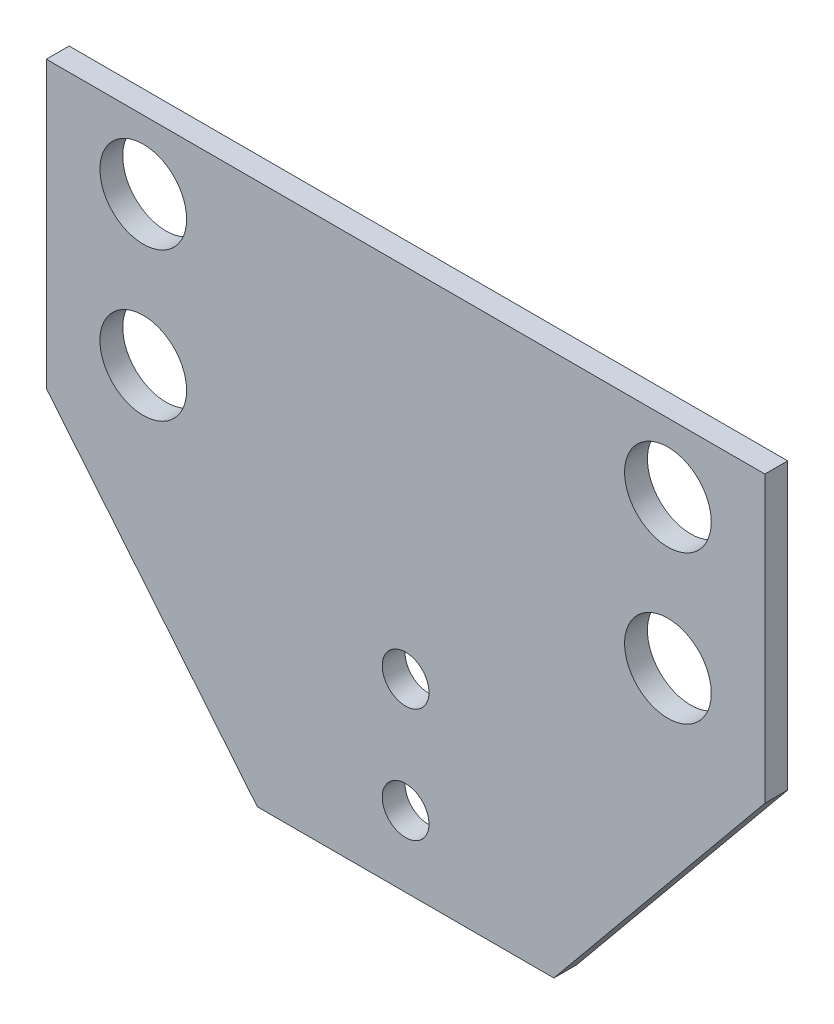
SolidWorks part; units mm, degrees
ref_plane "Front Plane" through (0, 0, 0) normal (0, 0, 1) x (1, 0, 0)
ref_plane "Top Plane" through (0, 0, 0) normal (0, 1, 0) x (1, 0, 0)
ref_plane "Right Plane" through (0, 0, 0) normal (1, 0, 0) x (0, 0, -1)
sketch "Sketch1" plane through (0, 0, 0) normal (0, 0, 1) x (1, 0, 0)
  line L0 (0, 0) -> (0, 60.5723) construction
  line L1 (0, -55) -> (0, 55) construction
  line L2 (0, 0) -> (-55.7657, 0) construction
  line L3 (31.5, 10) -> (-31.5, 10)
  line L4 (-31.5, 10) -> (-31.5, -15)
  line L5 (-31.5, -15) -> (31.5, -15)
  line L6 (31.5, 10) -> (31.5, -15)
  line L7 (0, -37.5157) -> (-13, -37.5157)
  line L8 (0, -37.5157) -> (13, -37.5157)
  line L9 (-13, -37.5157) -> (-31.5, -15)
  line L10 (13, -37.5157) -> (31.5, -15)
  line L11 (55, 0) -> (-55, 0) construction
  circle A4 centre (0, -21.3221) radius 2.05
  circle A5 centre (0, -31.3) radius 2.05
  circle A6 centre (-23, 4) radius 3.3
  circle A7 centre (-23, 4) radius 3.8
  circle A8 centre (-23, -9) radius 3.3
  circle A9 centre (-23, -9) radius 3.8
  circle A10 centre (23, -9) radius 3.8
  circle A11 centre (23, -9) radius 3.3
  circle A12 centre (23, 4) radius 3.3
  circle A13 centre (23, 4) radius 3.8
  point P5 (-23, 4)
  point P6 (-23, -9)
  point P12 (0, -37.5157)
  point P17 (0, -15)
  point P21 (0, 10)
  dimension "D3" = 13
  dimension "D7" = 6
  dimension "D8" = 6.6
  dimension "D9" = 4.1
  dimension "D10" = 4.1
  dimension "D11" = 46
  dimension "D2" = 6
  dimension "D4" = 63
  dimension "D5" = 25
  dimension "D6" = 13
extrude "Boss-Extrude1" add sketch "Sketch1" along normal blind 2 contours L6 L3 L4 L5 A8 region at (0, -2.5, 0)
extrude "Boss-Extrude2" add sketch "Sketch1<3>" along normal blind 2 contours L8 L10 L5 L9 L7 A5 A4 region at (0, -24.6541, 0)
sketch "Sketch1<3>" plane through (0, 0, 0) normal (0, 0, 1) x (1, 0, 0) same geometry as "Sketch1"
